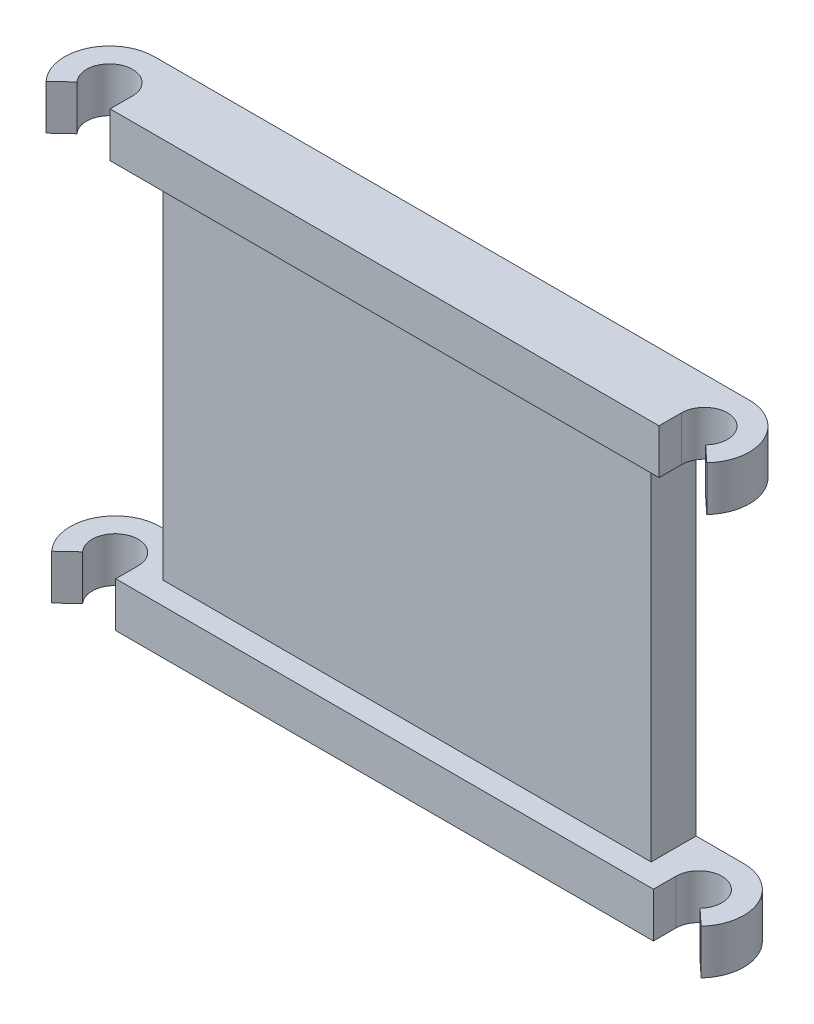
SolidWorks part; units mm, degrees
ref_plane "Płaszczyzna przednia" through (0, 0, 0) normal (0, 0, 1) x (1, 0, 0)
ref_plane "Płaszczyzna górna" through (0, 0, 0) normal (0, 1, 0) x (1, 0, 0)
ref_plane "Płaszczyzna prawa" through (0, 0, 0) normal (1, 0, 0) x (0, 0, -1)
sketch "Szkic1" plane through (0, 0, 0) normal (0, 0, 1) x (1, 0, 0)
  line L0 (0, 36) -> (0, -36) construction
  line L1 (-53, 36) -> (53, 36) construction
  line L2 (-52, -36) -> (52, -36) construction
  line L3 (-43.5, -36) -> (-43.5, 36) construction
  line L4 (43.5, 36) -> (43.5, -36) construction
  circle A0 centre (0, 0) radius 44 construction
  dimension "D5" = 88
  dimension "D1" = 106
  dimension "D2" = 104
  dimension "D3" = 72
  dimension "D4" = 8.5
ref_plane "Płaszczyzna1" through (0, -36, 0) normal (0, 1, 0) x (1, 0, 0)
sketch "Szkic2" plane through (0, -36, 0) normal (0, 1, 0) x (1, 0, 0)
  line L0 (-52, 0) -> (52, 0) construction
  line L1 (52, 8) -> (0, 8)
  line L2 (0, 8) -> (0, -4)
  line L3 (0, -4) -> (47.9, -4)
  line L4 (47.9, -4) -> (47.9, 0)
  line L5 (55, -2.7946) -> (57.8537, -5.453)
  arc A0 (47.9, 0) -> (55, -2.7946) centre (52, 0) cw
  arc A1 (57.8537, -5.453) -> (52, 8) centre (52, 0) ccw
  dimension "D1" = 4.1
  dimension "D2" = 8
  dimension "D3" = 4
  dimension "D4" = 7.1
extrude "Mid Clip" add sketch "Szkic2" along normal blind 4 and the other way blind 4
ref_plane "Płaszczyzna2" through (0, 36, 0) normal (0, 1, 0) x (1, 0, 0)
sketch "Szkic3" plane through (0, 36, 0) normal (0, 1, 0) x (1, 0, 0)
  line L0 (-53, 0) -> (53, 0) construction
  line L1 (53, 8) -> (0, 8)
  line L2 (0, 8) -> (0, -4)
  line L3 (0, -4) -> (48.9, -4)
  line L4 (48.9, 0) -> (48.9, -4)
  line L5 (56, -2.7946) -> (58.8537, -5.453)
  line L6 (47.9, -4) -> (47.9, 0) construction
  line L7 (55, -2.7946) -> (56, -2.7946) construction
  line L8 (-52, 0) -> (52, 0) construction
  arc A0 (48.9, 0) -> (56, -2.7946) centre (53, 0) cw
  arc A1 (53, 8) -> (58.8537, -5.453) centre (53, 0) cw
  arc A2 (57.8537, -5.453) -> (52, 8) centre (52, 0) ccw construction
  arc A3 (55, -2.7946) -> (47.9, 0) centre (52, 0) ccw construction
extrude "Rear Clip" add sketch "Szkic3" along normal blind 4 and the other way blind 4 separate body
sketch "Szkic4" plane through (0, 0, -8) normal (0, 0, -1) x (-1, 0, 0)
  line L0 (0, -32) -> (-43.5, -32)
  line L1 (-43.5, 36) -> (-43.5, -36) construction
  line L2 (-52, -32) -> (0, -32) construction
  line L3 (-43.5, -32) -> (-43.5, 32)
  line L4 (-53, 32) -> (0, 32) construction
  line L5 (-43.5, 32) -> (0, 32)
  line L6 (0, 32) -> (0, -32)
extrude "Dodanie-wyciągnięcie3" add sketch "Szkic4" against normal blind 8
mirror "Lustro2" about plane through (0, -40, -8) normal (-1, 0, 0) of "Mid Clip", "Dodanie-wyciągnięcie3", "Rear Clip"
